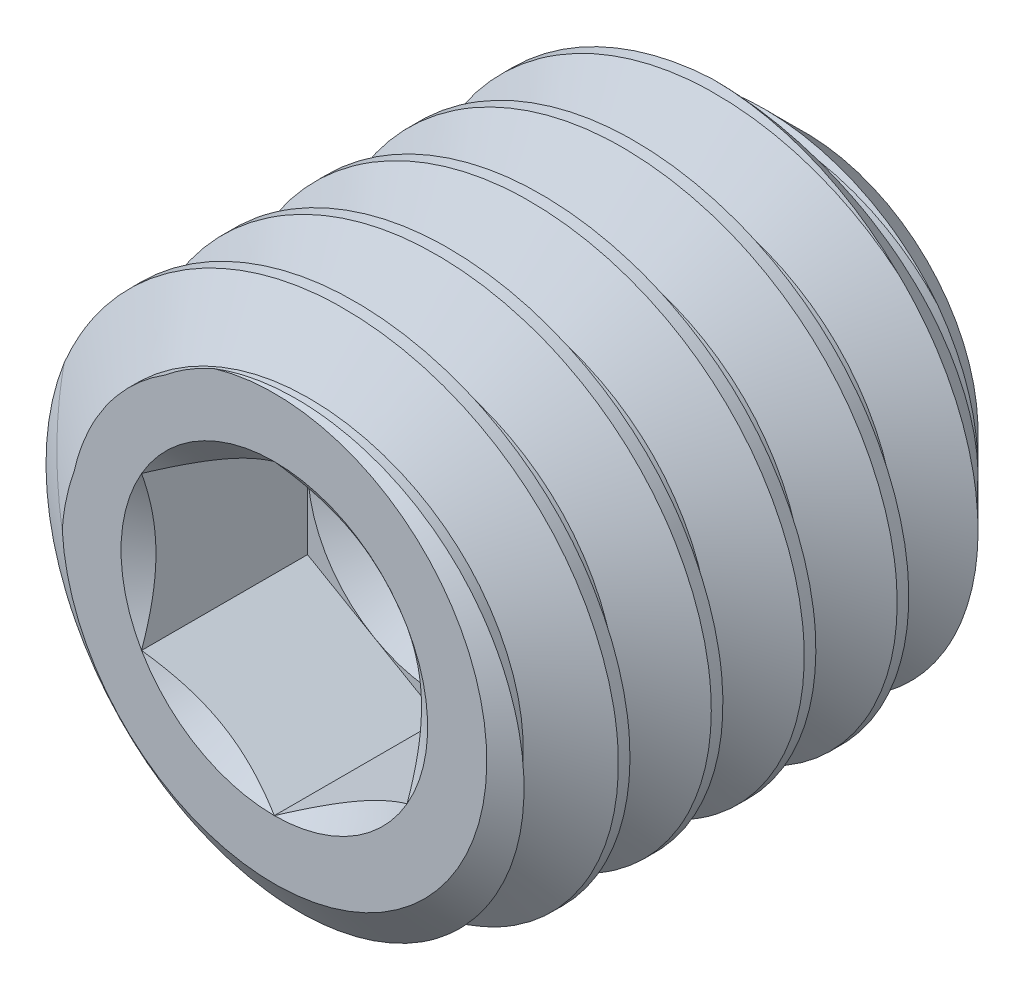
SolidWorks part; units mm, degrees
ref_plane "Front" through (0, 0, 0) normal (0, 0, 1) x (1, 0, 0)
ref_plane "Top" through (0, 0, 0) normal (0, 1, 0) x (1, 0, 0)
ref_plane "Right" through (0, 0, 0) normal (1, 0, 0) x (0, 0, -1)
sketch "Sketch22" plane through (0, 0, 0) normal (1, 0, 0) x (0, 0, -1)
  line L0 (-2, 0) -> (-2, 1.6)
  line L1 (-2, 1.6) -> (-1.7199, 2)
  line L2 (-1.7199, 2) -> (1.3, 2)
  line L3 (1.3, 2) -> (2, 1.3)
  line L4 (-0.21, 2) -> (-0.21, -2) construction
  line L5 (2, 0) -> (-2, 0)
  line L6 (-2, 1.6) -> (-2, -1.6) construction
  line L7 (2, 0) -> (2, 1.3)
  point P11 (-0.21, 0)
  dimension "Length" = 4
  dimension "D3" = 35
  dimension "D6" = 45
  dimension "Dia" = 4
  dimension "D1" = 3.2
  dimension "D2" = 0.7
revolve "Revolve1" add sketch "Sketch22" angle 360 about L5
ref_plane "Plane1" through (0, 0, -2) normal (0, 0, 1) x (1, 0, 0)
sketch "Sketch27" plane through (0, 0, -2) normal (0, 0, 1) x (1, 0, 0)
  circle A0 centre (0, 0) radius 2 construction
  circle A1 centre (0, 0) radius 2
curve "Helix/Spiral1" pitch 0.7 height 4.7 radius 2 centre (0, 0, -2) axis (0, 0, 1) start towards (0, 1, 0)
sketch "Sketch28" plane through (0, 0, 0) normal (1, 0, 0) x (0, 0, -1)
  line L0 (2, 2) -> (2.6125, 2)
  line L1 (2.6125, 2) -> (2.35, 1.5453)
  line L2 (2.35, 1.5453) -> (2.2625, 1.5453)
  line L3 (2.2625, 1.5453) -> (2, 2)
  line L4 (2.1313, 1.7727) -> (2.4813, 1.7727) construction
  line L6 (-1.7199, 2) -> (1.3, 2) construction
  dimension "D1" = 0.0875
  dimension "D3" = 60
  dimension "D2" = 0.35
sweep "Cut-Sweep2" cut profiles "Sketch28" path "Helix/Spiral1" align with end faces yes
sketch "Sketch23" plane through (0, 0, 2) normal (0, 0, 1) x (1, 0, 0)
  line L1 (0, 1.1547) -> (-1, 0.5774)
  line L2 (-1, 0.5774) -> (-1, -0.5774)
  line L3 (-1, -0.5774) -> (0, -1.1547)
  line L4 (0, -1.1547) -> (1, -0.5774)
  line L5 (1, -0.5774) -> (1, 0.5774)
  line L6 (1, 0.5774) -> (0, 1.1547)
  circle A0 centre (0, 0) radius 1 construction
  dimension "Hex" = 2
extrude "Cut-Extrude10" cut sketch "Sketch23" against normal blind 1.25
sketch "Sketch24" plane through (0, 0, 2) normal (0, 0, 1) x (1, 0, 0)
  circle A0 centre (0, 0) radius 1.1547
extrude "Cut-Extrude11" cut sketch "Sketch24" against normal through all draft 55
sketch "Sketch26" plane through (0, 0, 0.75) normal (0, 0, 1) x (1, 0, 0)
  circle A0 centre (0, 0) radius 1 construction
  circle A1 centre (0, 0) radius 1
extrude "Cut-Extrude12" cut sketch "Sketch26" against normal through all draft 60
sketch "Sketch30" plane through (0, 0, 0) normal (1, 0, 0) x (0, 0, -1)
  line L0 (-1.7199, 2) -> (1.3, 2) construction
  line L1 (-2, 0) -> (-2, 1.6) construction
  line L2 (2, 0) -> (2, 1.3) construction
  point P0 (-2, 2)
  point P1 (2, 2)
  point P2 (2, -2)
  point P11 (0.25, -2)
  dimension "D1" = 1.75
equation "\"D1@Sketch28\" = \"D4@Helix/Spiral1\" * .125"
equation "\"D2@Sketch28\" = \"D4@Helix/Spiral1\" * .5"
equation "\"D3@Helix/Spiral1\" = \"Length@Sketch22\" + \"D4@Helix/Spiral1\""
equation "\"D1@Sketch30\" = \"D4@Helix/Spiral1\" * 2.5"
equation "\"hex Depth@Cut-Extrude10\" = \"Hex@Sketch23\" * .625"
equation "\"D1@Sketch22\" = \"Dia@Sketch22\" * .8"
equation "\"D2@Sketch22\" = \"D4@Helix/Spiral1\""
